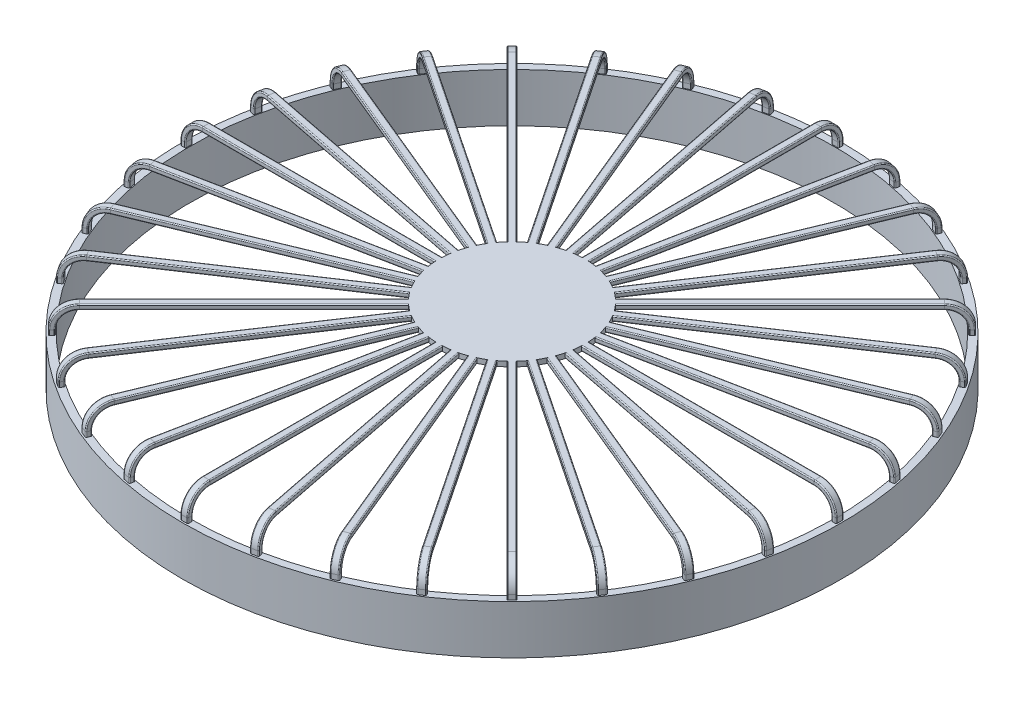
SolidWorks part; units mm, degrees
ref_plane "前视基准面" through (0, 0, 0) normal (0, 0, 1) x (1, 0, 0)
ref_plane "上视基准面" through (0, 0, 0) normal (0, 1, 0) x (1, 0, 0)
ref_plane "右视基准面" through (0, 0, 0) normal (1, 0, 0) x (0, 0, -1)
sketch "草图1" plane through (0, 0, 0) normal (0, 1, 0) x (1, 0, 0)
  circle A0 centre (0, 0) radius 67.5
  circle A1 centre (0, 0) radius 66
  dimension "D1" = 135
  dimension "D2" = 132
extrude "凸台-拉伸1" add sketch "草图1" along normal blind 10
ref_plane "基准面4" through (0, 10, 0) normal (0, 1, 0) x (1, 0, 0)
sketch "草图2" plane through (0, 10, 0) normal (0, 1, 0) x (1, 0, 0)
  line L0 (-96.3021, 0) -> (114.8114, 0) construction
  circle A0 centre (0, 0) radius 67.5
  point P7 (-67.5, 0)
sketch "草图3" plane through (0, 0, 0) normal (0, 0, 1) x (1, 0, 0)
  line L0 (-67.5, 10) -> (-67.5, 15) construction
  line L1 (-67.5, 15) -> (0, 15) construction
  line L2 (0, 0) -> (0, 33.8091) construction
  line L3 (-67.5, 0) -> (67.5, 0) construction
  line L4 (-66.65, 10) -> (-66.65, 11)
  line L5 (-96.3021, 10) -> (114.8114, 10) construction
  line L6 (-62.65, 15) -> (0, 15)
  arc A0 (-66.65, 11) -> (-62.65, 15) centre (-62.65, 11) cw
  point P14 (-66.65, 15)
  dimension "D3" = 4
  dimension "D1" = 5
  dimension "D2" = 66.65
sketch "草图4" plane through (0, 10, 0) normal (0, 1, 0) x (1, 0, 0)
  line L1 (-66.95, 0.75) -> (-66.35, 0.75)
  line L2 (-67.15, 0.55) -> (-67.15, -0.55)
  line L3 (-66.95, -0.75) -> (-66.35, -0.75)
  line L4 (-66.15, 0.55) -> (-66.15, -0.55)
  line L5 (-67.15, 0.75) -> (-66.15, -0.75) construction
  line L6 (-67.15, -0.75) -> (-66.15, 0.75) construction
  arc A2 (-67.15, -0.55) -> (-66.95, -0.75) centre (-66.95, -0.55) ccw
  arc A3 (-66.35, -0.75) -> (-66.15, -0.55) centre (-66.35, -0.55) ccw
  arc A4 (-66.35, 0.75) -> (-66.15, 0.55) centre (-66.35, 0.55) cw
  arc A5 (-66.95, 0.75) -> (-67.15, 0.55) centre (-66.95, 0.55) ccw
  point P0 (-66.65, 0)
  dimension "D1" = 1
  dimension "D2" = 1.5
  dimension "D3" = 0.2
sweep "扫描3" add profiles "草图4" path "草图3"
sketch "草图5" plane through (0, 10, 0) normal (0, 1, 0) x (1, 0, 0)
ref_axis "基准轴1" through (0, 10, 0) along (0, 1, 0)
pattern_circular "阵列(圆周)1" count 32 over 360 about axis through (0, 10, 0) along (0, 1, 0) of "扫描3"
ref_plane "基准面5" through (0, 15.5, 0) normal (0, 1, 0) x (1, 0, 0)
sketch "草图6" plane through (0, 15.5, 0) normal (0, 1, 0) x (1, 0, 0)
  circle A0 centre (0, 0) radius 15
  dimension "D1" = 30
extrude "凸台-拉伸2" add sketch "草图6" against normal blind 1
